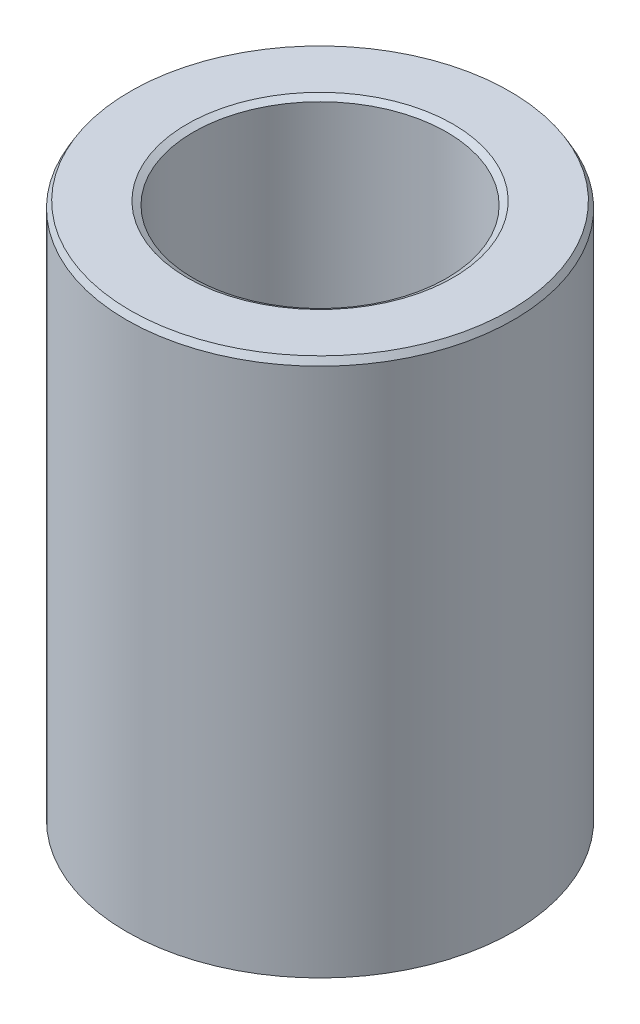
SolidWorks part; units mm, degrees
ref_plane "Front Plane" through (0, 0, 0) normal (0, 0, 1) x (1, 0, 0)
ref_plane "Top Plane" through (0, 0, 0) normal (0, 1, 0) x (1, 0, 0)
ref_plane "Right Plane" through (0, 0, 0) normal (1, 0, 0) x (0, 0, -1)
sketch "Sketch1" plane through (0, 0, 0) normal (0, 1, 0) x (1, 0, 0)
  circle A0 centre (0, 0) radius 37.5
  dimension "SLEEVE_OD" = 75
extrude "Boss-Extrude1" add sketch "Sketch1" along normal blind 104.6404
sketch "Sketch2" plane through (0, 0, 0) normal (0, 1, 0) x (1, 0, 0)
  circle A0 centre (0, 0) radius 24.5471
  dimension "BORE_D" = 49.0941
extrude "Cut-Extrude1" cut sketch "Sketch2" along normal through all
chamfer "Chamfer1" distance 1.2374 angle 30 4 edges at (0, 104.6404, 24.5471) (0, 0, 24.5471) (0, 0, 37.5) (0, 104.6404, 37.5) first distance on face at (0, 104.6404, 24.5471) first distance on face at (0, 0, 24.5471) first distance on face at (0, 104.6404, 37.5)
